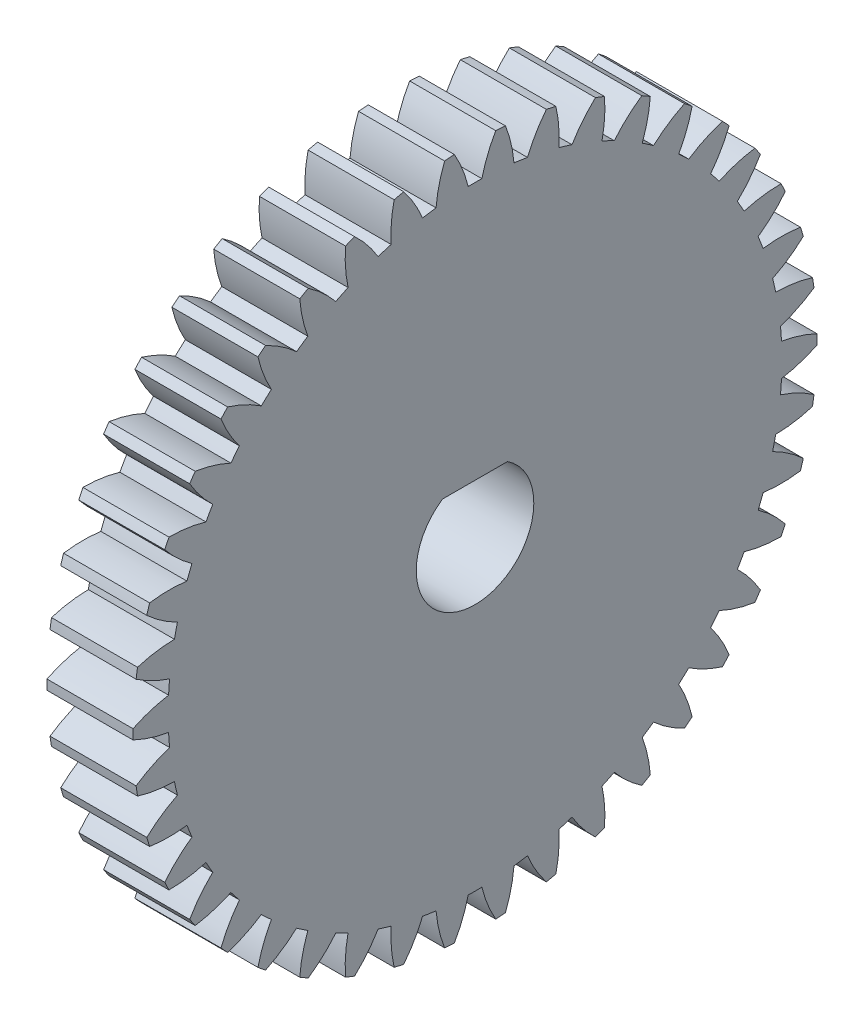
SolidWorks part; units mm, degrees
ref_plane "Plane1" through (0, 0, 0) normal (0, 0, 1) x (1, 0, 0)
ref_plane "Plane2" through (0, 0, 0) normal (0, 1, 0) x (1, 0, 0)
ref_plane "Plane3" through (0, 0, 0) normal (1, 0, 0) x (0, 0, -1)
sketch "HoldingSke" plane through (0, 0, 0) normal (0, 1, 0) x (1, 0, 0)
  line L0 (0, 0) -> (604.0281, -543.8694)
  line L1 (-15, 0) -> (100, 0) construction
  line L2 (0, 0) -> (-2.1039, 2.3779)
  line L3 (0, 0) -> (-11.863, 4.5341)
  line L4 (0, 0) -> (6.4178, 5.7786)
  line L5 (0, 0) -> (-47.5972, -17.7524)
  line L6 (0, 0) -> (-3.6426, -2.4577)
  line L7 (-2.1039, 2.3779) -> (8.8308, 51.9871)
  line L8 (-76.2, 54.61) -> (-75.184, 54.61)
  line L9 (-71.009, 38.7566) -> (-53.1078, 45.2721)
  line L10 (-76.2, 71.12) -> (104.1128, 71.12)
  line L11 (0, 0) -> (-4.3942, 0)
  line L12 (-76.2, 101.6) -> (-76.1716, 101.6)
  line L13 (24.9733, 27.94) -> (52.9518, 28.4284)
  line L14 (24.9733, 27.94) -> (25.0241, 27.9398)
  line L15 (24.9733, 27.94) -> (100.4021, 29.52)
  circle A0 centre (0, 0) radius 0.3969
  circle A1 centre (0, 0) radius 15.6655
  circle A2 centre (0, 0) radius 38.1
  circle A3 centre (0, 0) radius 0.3969
  dimension "MHD" = 31.3309
  dimension "Hub_dia" = 76.2
  dimension "Bore" = 0.7937
  dimension "MBD" = 0.7937
  dimension "Num_teeth" = 42
  dimension "Pitch_radius" = 180.3128
  dimension "Pitch" = 812.8
  dimension "Width" = 4.3942
  dimension "Overall_len" = 50.8
  dimension "Show_teeth" = 42
  dimension "Thickness" = 4.3942
  dimension "OAL" = 50.8001
  dimension "T_dim" = 1.016
  dimension "Ap" = 20
  dimension "H" = 19.05
  dimension "Backlash" = 0.0284
  dimension "Addendum_fac" = 1
  dimension "Dedendum_fac" = 1.2
  dimension "Clearance_fac" = 0.2
  dimension "Dedendum_add" = 0.0508
sketch "BasProSke" plane through (0, 0, 0) normal (0, 1, 0) x (1, 0, 0)
  line L0 (-10, 0) -> (60, 0) construction
  line L1 (0, 0) -> (0, 17.4625)
  line L2 (0, 0) -> (4.3942, 0)
  line L3 (4.3942, 0) -> (4.3942, 17.4625)
  line L4 (4.3942, 17.4625) -> (0, 17.4625)
  dimension "Diameter" = 34.925
  dimension "Thickness" = 4.3942
revolve "Base-Revolve" add sketch "BasProSke" angle 360 about L0
sketch "TooCutSke" plane through (0, 0, 0) normal (1, 0, 0) x (0, 0, -1)
  line L1 (0, 0) -> (0, 107) construction
  line L2 (0, 0) -> (-0.673, 16.6552) construction
  line L3 (0, 0) -> (-2.4898, 33.2246) construction
  line L4 (-0.673, 16.6552) -> (-1.2449, 16.6123) construction
  arc A0 (0.3488, 15.6616) -> (-0.3488, 15.6616) centre (0, 0) ccw
  arc A1 (1.0703, 17.4551) -> (-1.0703, 17.4551) centre (0, 0) ccw
  circle A2 centre (0, 0) radius 16.6687 construction
  circle A3 centre (0, 0) radius 15.6635 construction
  arc A4 (-0.3488, 15.6616) -> (-1.0703, 17.4551) centre (-6.8299, 14.096) ccw
  arc A5 (1.0703, 17.4551) -> (0.3488, 15.6616) centre (6.8299, 14.096) ccw
  dimension "Root_dia" = 31.3309
  dimension "Overcut_dia" = 34.9758
  dimension "Pitch_dia" = 33.3375
  dimension "Base_dia" = 31.327
  dimension "Flank_rad" = 6.6675
  dimension "Half_ang" = 4.286
  dimension "Half_CT" = 0.5735
extrude "ToothCut" cut sketch "TooCutSke" along normal through all
fillet "Breaks" [suppressed] radius 0.0159 tangent propagation no
fillet "RootFillets" [suppressed] radius 0.2095
pattern_circular "TeethCuts" count 42 every 8.571 about axis through (-10, 0, 0) along (1, 0, 0) of "ToothCut", "RootFillets", "Breaks"
sketch "HubNeaOneSke" plane through (0, 0, 0) normal (-1, 0, 0) x (0, 0, 1)
  circle A0 centre (0, 0) radius 15.6655
  dimension "Diameter" = 31.3309
extrude "HubNearOne" [suppressed] add sketch "HubNeaOneSke" along normal blind 46.4059
sketch "HubNeaBotSke" plane through (0, 0, 0) normal (-1, 0, 0) x (0, 0, 1)
  circle A0 centre (0, 0) radius 15.6655
  dimension "Diameter" = 31.3309
extrude "HubNearBoth" [suppressed] add sketch "HubNeaBotSke" along normal blind 23.2029
ref_plane "FarPln" through (4.3942, 0, 0) normal (1, 0, 0) x (0, 0, -1)
sketch "HubFarSke" plane through (4.3942, 0, 0) normal (1, 0, 0) x (0, 0, -1)
  circle A0 centre (0, 0) radius 15.6655
  dimension "Diameter" = 31.3309
extrude "HubFar" [suppressed] add sketch "HubFarSke" along normal blind 23.2029
sketch "BorSke" plane through (0, 0, 0) normal (1, 0, 0) x (0, 0, -1)
  circle A0 centre (0, 0) radius 0.3969
  dimension "Diameter" = 0.7937
extrude "Bore" cut sketch "BorSke" along normal mid plane 101.6001
sketch "KeySke" plane through (0, 0, 0) normal (1, 0, 0) x (0, 0, -1)
  line L0 (-0.127, 0) -> (-0.127, 0.6191)
  line L1 (-0.127, 0.6191) -> (0.127, 0.6191)
  line L2 (0.127, 0.6191) -> (0.127, 0)
  line L3 (0, 0) -> (0, 34) construction
  line L4 (-0.127, 0) -> (0.127, 0)
  dimension "Offset" = 0.6191
  dimension "Width" = 0.254
extrude "Keyway" [suppressed] cut sketch "KeySke" along normal mid plane 101.6001
pattern_circular "Keyway2" [suppressed] count 2 every 90 about axis through (-10, 0, 0) along (1, 0, 0)
sketch "Sketch1" plane through (4.3942, 0, 0) normal (1, 0, 0) x (0, 0, -1)
  line L0 (-1.6583, 2.5) -> (1.6583, 2.5)
  arc A0 (-1.6583, 2.5) -> (1.6583, 2.5) centre (0, 0) ccw
  dimension "D1" = 6
  dimension "D2" = 2.5
extrude "Cut-Extrude1" cut sketch "Sketch1" against normal blind 7.366
equation "' \"Pitch@HoldingSke\" = 4"
equation "' \"Num_teeth@HoldingSke\" = 12"
equation "' \"Ap@HoldingSke\" =  20"
equation "' \"Width@HoldingSke\" = 0.5"
equation "' \"Hub_dia@HoldingSke\"= 1"
equation "' \"Overall_len@HoldingSke\" = 1.0"
equation "' \"Bore@HoldingSke\" = 0.75"
equation "' \"T_dim@HoldingSke\" = 0.85"
equation "' \"Width@KeySke\" = 0.25"
equation "' \"Show_teeth@HoldingSke\" = 13"
equation "' \"Backlash@HoldingSke\" = 0.009"
equation "' \"Addendum_fac@HoldingSke\" = 1.0"
equation "' \"Dedendum_fac@HoldingSke\" = 1.25"
equation "' \"Dedendum_add@HoldingSke\" = 0.00005"
equation "' \"Clearance_fac@HoldingSke\" = 0.25"
equation "' \"Pitch@HoldingSke\" = 0.5"
equation "' \"Num_teeth@HoldingSke\" = 23"
equation "' \"Show_teeth@HoldingSke\" = 23"
equation "' \"Backlash@HoldingSke\" = 0.0375"
equation "\"Overcut_dia@TooCutSke\" = (\"Num_teeth@HoldingSke\" + 2 * \"Addendum_fac@HoldingSke\") / \"Pitch@HoldingSke\" + 0.002"
equation "\"Pitch_dia@TooCutSke\" = \"Num_teeth@HoldingSke\" / \"Pitch@HoldingSke\""
equation "\"Base_dia@TooCutSke\" = \"Num_teeth@HoldingSke\" / \"Pitch@HoldingSke\" * cos((\"Ap@HoldingSke\"  * 3.14159265 / 180))"
equation "\"Root_dia@TooCutSke\" = (\"Num_teeth@HoldingSke\" + 2) / \"Pitch@HoldingSke\" - 2 * (\"Addendum_fac@HoldingSke\" + \"Dedendum_fac@HoldingSke\") / \"Pitch@HoldingSke\" - \"Dedendum_add@HoldingSke\" * 2"
equation "\"Half_ang@TooCutSke\" = 180 / \"Num_teeth@HoldingSke\""
equation "\"Half_CT@TooCutSke\" = \"Num_teeth@HoldingSke\" / \"Pitch@HoldingSke\" * sin((3.14159265 / 2 / \"Num_teeth@HoldingSke\")) / 2 - 7 * \"Backlash@HoldingSke\" / 4"
equation "\"Flank_rad@TooCutSke\" = \"Num_teeth@HoldingSke\" / \"Pitch@HoldingSke\" / 5"
equation "\"Radius@RootFillets\" = \"Clearance_fac@HoldingSke\" / \"Pitch@HoldingSke\" + \"Dedendum_add@HoldingSke\""
equation "\"Break_rad@Breaks\" = 0.02 / \"Pitch@HoldingSke\""
equation "\"Thickness@HoldingSke\" = \"Width@HoldingSke\""
equation "\"OAL@HoldingSke\" = \"Thickness@HoldingSke\""
equation "\"MHD@HoldingSke\" = (\"Num_teeth@HoldingSke\" + 2) / \"Pitch@HoldingSke\" - 2 * (\"Addendum_fac@HoldingSke\" + \"Dedendum_fac@HoldingSke\")  / \"Pitch@HoldingSke\" - \"Dedendum_add@HoldingSke\" * 2"
equation "\"MBD@HoldingSke\" = (\"Num_teeth@HoldingSke\" + 2) / \"Pitch@HoldingSke\" - 2 * (\"Addendum_fac@HoldingSke\" + \"Dedendum_fac@HoldingSke\")  / \"Pitch@HoldingSke\" - \"Dedendum_add@HoldingSke\" * 2 - 0.002"
equation "\"MHD@HoldingSke\" = ((sgn( \"MHD@HoldingSke\" - \"Hub_dia@HoldingSke\" )-1)*( \"MHD@HoldingSke\" - \"Hub_dia@HoldingSke\" ))/-2+ \"Hub_dia@HoldingSke\""
equation "\"MBD@HoldingSke\" = ((sgn( \"MBD@HoldingSke\" - \"Bore@HoldingSke\" )-1)*( \"MBD@HoldingSke\" - \"Bore@HoldingSke\" ))/-2+ \"Bore@HoldingSke\""
equation "\"OAL@HoldingSke\" = ((sgn( \"OAL@HoldingSke\" - \"Overall_len@HoldingSke\" )+1)*( \"OAL@HoldingSke\" - \"Overall_len@HoldingSke\" ))/2 + \"Overall_len@HoldingSke\" + 0.000002"
equation "\"Num_teeth@TeethCuts\" = int( \"Show_teeth@HoldingSke\" ) + 1"
equation "\"Num_teeth@TeethCuts\" = ((sgn( \"Num_teeth@TeethCuts\" - \"Num_teeth@HoldingSke\" )-1)*( \"Num_teeth@TeethCuts\" - \"Num_teeth@HoldingSke\" ))/-2+ \"Num_teeth@HoldingSke\""
equation "\"Num_teeth@TeethCuts\" = ((sgn( \"Num_teeth@TeethCuts\" - 2.0)+1)*( \"Num_teeth@TeethCuts\" - 2.0))/2 +2.0"
equation "\"Angle@TeethCuts\" = 360.0 / \"Num_teeth@HoldingSke\""
equation "\"Diameter@BasProSke\" = (\"Num_teeth@HoldingSke\" + 2 * \"Addendum_fac@HoldingSke\") / \"Pitch@HoldingSke\""
equation "\"Thickness@BasProSke\"  = \"Thickness@HoldingSke\""
equation "' \"Fillet_rad@BasProSke\" =  \"Thickness@HoldingSke\" * 0.05"
equation "\"MHD@HoldingSke\" = ((sgn( \"MHD@HoldingSke\" - \"Root_dia@TooCutSke\" )-1)*( \"MHD@HoldingSke\" - \"Root_dia@TooCutSke\" ))/-2+ \"Root_dia@TooCutSke\""
equation "\"Diameter@HubNeaOneSke\" = \"MHD@HoldingSke\""
equation "\"Length@HubNearOne\" = \"OAL@HoldingSke\" - \"Thickness@BasProSke\""
equation "\"Diameter@HubNeaBotSke\" = \"MHD@HoldingSke\""
equation "\"Length@HubNearBoth\" = ( \"OAL@HoldingSke\" - \"Thickness@BasProSke\" ) / 2.0"
equation "\"Thickness@FarPln\" = \"Thickness@BasProSke\""
equation "\"Diameter@HubFarSke\" = \"MHD@HoldingSke\""
equation "\"Length@HubFar\" = ( \"OAL@HoldingSke\" - \"Thickness@BasProSke\" ) / 2.0"
equation "\"Diameter@BorSke\" = \"MBD@HoldingSke\""
equation "\"D1@Bore\" = \"OAL@HoldingSke\" * 2.0"
equation "\"D1@Keyway\" = \"OAL@HoldingSke\" * 2.0"
equation "\"Offset@KeySke\" = \"T_dim@HoldingSke\" - \"MBD@HoldingSke\" / 2.0"
